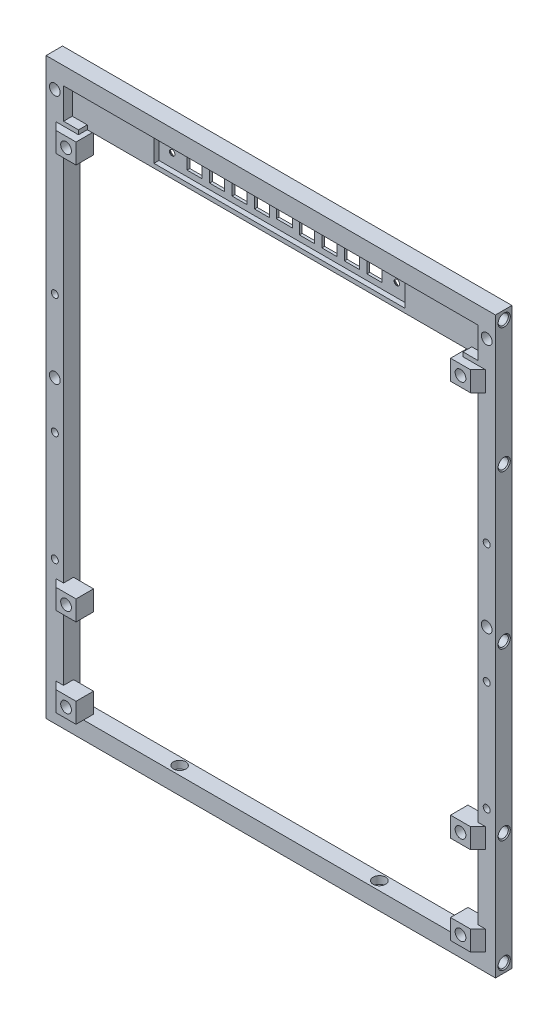
SolidWorks part; units mm, degrees
ref_plane "Front Plane" through (0, 0, 0) normal (0, 0, 1) x (1, 0, 0)
ref_plane "Top Plane" through (0, 0, 0) normal (0, 1, 0) x (1, 0, 0)
ref_plane "Right Plane" through (0, 0, 0) normal (1, 0, 0) x (0, 0, -1)
sketch "Sketch1" plane through (0, 0, 0) normal (0, 0, 1) x (1, 0, 0)
  line L1 (-90, -115) -> (90, -115)
  line L2 (-90, -115) -> (-90, 115)
  line L3 (-90, 115) -> (90, 115)
  line L4 (90, -115) -> (90, 115)
  line L5 (-90, -115) -> (90, 115) construction
  line L6 (-90, 115) -> (90, -115) construction
  line L7 (-83, -108) -> (83, -108)
  line L8 (-83, -108) -> (-83, 108)
  line L9 (-83, 108) -> (83, 108)
  line L10 (83, -108) -> (83, 108)
  line L11 (-83, -108) -> (83, 108) construction
  line L12 (-83, 108) -> (83, -108) construction
  point P0 (0, 0)
  point P6 (0, 0)
  dimension "D1" = 180
  dimension "D2" = 230
  dimension "D3" = 7
  dimension "D4" = 7
extrude "Boss-Extrude1" add sketch "Sketch1" along normal blind 7
sketch "Sketch2" plane through (-90, 0, 0) normal (-1, 0, 0) x (0, 0, 1)
  line L0 (3.5, 111.5) -> (3.5, -111.5) construction
  line L1 (7, 115) -> (0, 115) construction
  circle A0 centre (3.5, -111.5) radius 2.05
  circle A2 centre (3.5, 111.5) radius 2.05
  circle A3 centre (3.5, 61.5) radius 2.05
  circle A4 centre (3.5, -66.5) radius 2.05
  point P2 (3.5, 0)
  point P7 (3.5, 115)
  dimension "D2" = 4.1
  dimension "D3" = 50
  dimension "D4" = 45
  dimension "D1" = 3.5
extrude "Cut-Extrude1" cut sketch "Sketch2" against normal blind 6
mirror "Mirror1" about plane through (0, 0, 0) normal (1, 0, 0) of "Cut-Extrude1"
sketch "Sketch3" plane through (0, -108, 0) normal (0, 1, 0) x (1, 0, 0)
  line L0 (0, 0) -> (0, -7) construction
  line L1 (-83, 0) -> (83, 0) construction
  line L2 (-83, -7) -> (83, -7) construction
  line L3 (40, -3.5) -> (-40, -3.5) construction
  circle A0 centre (40, -3.5) radius 1.35
  circle A1 centre (-40, -3.5) radius 1.35
  point P9 (0, -3.5)
  dimension "D1" = 2.7
  dimension "D2" = 80
extrude "Cut-Extrude2" cut sketch "Sketch3" against normal through all
sketch "Sketch4" plane through (0, -108, 0) normal (0, 1, 0) x (1, 0, 0)
  circle A0 centre (40, -3.5) radius 2.5
  circle A1 centre (-40, -3.5) radius 2.5
  dimension "D1" = 5
extrude "Cut-Extrude3" cut sketch "Sketch4" against normal blind 3
sketch "Sketch5" plane through (0, 0, 0) normal (0, 0, -1) x (-1, 0, 0)
  line L0 (-86.5, -115) -> (-86.5, 115) construction
  line L1 (90, -115) -> (-90, -115) construction
  line L2 (-90, 115) -> (90, 115) construction
  line L3 (-83, 0) -> (-90, 0) construction
  line L4 (-83, -108) -> (-83, 108) construction
  line L5 (-90, -115) -> (-90, 115) construction
  line L6 (0, 115) -> (0, -115) construction
  line L7 (83, -108) -> (-83, -108) construction
  circle A0 centre (-86.5, 34) radius 1.4
  circle A1 centre (86.5, 34) radius 1.4
  circle A2 centre (-86.5, -58) radius 1.4
  circle A3 centre (86.5, -58) radius 1.4
  point P12 (-86.5, 0)
  point P13 (-86.5, 0)
  dimension "D1" = 2.8
  dimension "D2" = 34
  dimension "D3" = 50
extrude "Cut-Extrude4" cut sketch "Sketch5" against normal through all
sketch "Sketch6" plane through (0, 0, 0) normal (0, 0, -1) x (-1, 0, 0)
  circle A0 centre (-86.5, 34) radius 2.5
  circle A1 centre (86.5, 34) radius 2.5
  circle A2 centre (-86.5, -58) radius 2.5
  circle A3 centre (86.5, -58) radius 2.5
  dimension "D1" = 5
extrude "Cut-Extrude5" cut sketch "Sketch6" against normal blind 3
sketch "Sketch7" plane through (0, 0, 0) normal (0, 0, -1) x (-1, 0, 0)
  line L0 (-83, 108) -> (-90, 108) construction
  line L1 (-90, -115) -> (-90, 115) construction
  line L2 (-86.5, 105) -> (-86.5, 5) construction
  line L3 (-90, 115) -> (90, 115) construction
  circle A0 centre (-86.5, 105) radius 2.15
  circle A1 centre (-86.5, 5) radius 2.15
  point P8 (-86.5, 108)
  dimension "D1" = 4.3
  dimension "D2" = 10
  dimension "D3" = 100
extrude "Cut-Extrude6" cut sketch "Sketch7" against normal through all
mirror "Mirror2" about plane through (0, 0, 0) normal (1, 0, 0) of "Cut-Extrude6"
sketch "Sketch8" plane through (0, 0, 3) normal (0, 0, -1) x (-1, 0, 0)
  line L2 (-87.9, 31.9288) -> (-87.9, 36.0712)
  line L4 (-85.1, 31.9288) -> (-85.1, 36.0712)
  line L5 (-87.9, 31.9288) -> (-85.1, 36.0712) construction
  line L6 (-87.9, 36.0712) -> (-85.1, 31.9288) construction
  line L8 (-87.9, -60.0712) -> (-87.9, -55.9288)
  line L10 (-85.1, -60.0712) -> (-85.1, -55.9288)
  line L11 (-87.9, -60.0712) -> (-85.1, -55.9288) construction
  line L12 (-87.9, -55.9288) -> (-85.1, -60.0712) construction
  circle A0 centre (-86.5, 34) radius 2.5 construction
  circle A1 centre (-86.5, -58) radius 2.5 construction
  circle A2 centre (-86.5, -58) radius 2.5 construction
  arc A3 (-85.1, 36.0712) -> (-87.9, 36.0712) centre (-86.5, 34) ccw
  arc A4 (-85.1, -55.9288) -> (-87.9, -55.9288) centre (-86.5, -58) ccw
  circle A5 centre (-86.5, 34) radius 1.4 construction
  circle A6 centre (-86.5, -58) radius 1.4 construction
  arc A7 (-87.9, -60.0712) -> (-85.1, -60.0712) centre (-86.5, -58) ccw
  arc A8 (-87.9, 31.9288) -> (-85.1, 31.9288) centre (-86.5, 34) ccw
  point P0 (-86.5, 34)
  point P8 (-86.5, -58)
extrude "Cut-Extrude7" cut sketch "Sketch8" against normal blind 0.2
sketch "Sketch9" plane through (0, 0, 3.2) normal (0, 0, -1) x (-1, 0, 0)
  line L0 (-85.1, 34) -> (-85.1, 36.0712) construction
  line L1 (-87.9, 32.6) -> (-85.1, 32.6)
  line L2 (-87.9, 32.6) -> (-87.9, 35.4)
  line L3 (-87.9, 35.4) -> (-85.1, 35.4)
  line L4 (-85.1, 32.6) -> (-85.1, 35.4)
  line L5 (-87.9, 32.6) -> (-85.1, 35.4) construction
  line L6 (-87.9, 35.4) -> (-85.1, 32.6) construction
  line L7 (-85.1, -60.0712) -> (-85.1, -55.9288) construction
  line L8 (-87.9, -59.4) -> (-85.1, -59.4)
  line L9 (-87.9, -59.4) -> (-87.9, -56.6)
  line L10 (-87.9, -56.6) -> (-85.1, -56.6)
  line L11 (-85.1, -59.4) -> (-85.1, -56.6)
  line L12 (-87.9, -59.4) -> (-85.1, -56.6) construction
  line L13 (-87.9, -56.6) -> (-85.1, -59.4) construction
  arc A0 (-85.1, 34) -> (-87.9, 34) centre (-86.5, 34) ccw construction
  point P0 (-86.5, 34)
  point P8 (-86.5, -58)
extrude "Cut-Extrude8" cut sketch "Sketch9" against normal blind 0.2
mirror "Mirror3" about plane through (0, 0, 0) normal (1, 0, 0) of "Cut-Extrude8", "Cut-Extrude7"
sketch "Sketch10" plane through (0, 0, 7) normal (0, 0, 1) x (1, 0, 0)
  line L0 (83, -108) -> (83, 108) construction
  line L1 (83, -108) -> (77, -108)
  line L2 (83, -108) -> (83, -102)
  line L3 (83, -102) -> (77, -102)
  line L4 (77, -108) -> (77, -102)
  line L5 (83, -78.5) -> (77, -78.5)
  line L6 (83, -78.5) -> (83, -72.5)
  line L7 (83, -72.5) -> (77, -72.5)
  line L8 (77, -78.5) -> (77, -72.5)
  line L9 (-83, -108) -> (83, -108) construction
  dimension "D1" = 6
  dimension "D2" = 35.5
extrude "Boss-Extrude2" add sketch "Sketch10" against normal offset from surface (5.5 mm away) 1.5 up to face at (-84.35, 5, 0)
sketch "Sketch11" plane through (0, 0, 1.5) normal (0, 0, -1) x (-1, 0, 0)
  line L0 (-83, -78.5) -> (-77, -72.5) construction
  line L2 (-83, -108) -> (-77, -102) construction
  circle A0 centre (-80, -75.5) radius 1.65
  circle A1 centre (-80, -105) radius 1.65
  dimension "D1" = 3.3
extrude "Cut-Extrude9" cut sketch "Sketch11" against normal through all
mirror "Mirror4" about plane through (0, 0, 0) normal (1, 0, 0) of "Cut-Extrude9", "Boss-Extrude2"
sketch "Sketch12" plane through (0, 0, 0) normal (0, 0, -1) x (-1, 0, 0)
  line L0 (83, 108) -> (83, -108) construction
  line L1 (-83, 108) -> (83, 108)
  line L2 (-83, 108) -> (-83, 94)
  line L3 (-83, 94) -> (83, 94)
  line L4 (83, 108) -> (83, 94)
  dimension "D1" = 14
extrude "Boss-Extrude3" add sketch "Sketch12" against normal blind 1.5
sketch "Sketch13" plane through (0, 0, 1.5) normal (0, 0, 1) x (1, 0, 0)
  line L0 (-83, 108) -> (83, 94) construction
  line L2 (-50.3, 95.7) -> (50.3, 95.7)
  line L3 (-50.3, 95.7) -> (-50.3, 106.3)
  line L4 (-50.3, 106.3) -> (50.3, 106.3)
  line L5 (50.3, 95.7) -> (50.3, 106.3)
  line L6 (-50.3, 95.7) -> (50.3, 106.3) construction
  line L7 (-50.3, 106.3) -> (50.3, 95.7) construction
  line L8 (-83, 94) -> (83, 94)
  line L9 (-83, 94) -> (-83, 108)
  line L10 (-83, 108) -> (83, 108)
  line L11 (83, 94) -> (83, 108)
  line L12 (-83, 94) -> (83, 108) construction
  line L13 (-83, 108) -> (83, 94) construction
  point P4 (0, 101)
  point P9 (0, 101)
  dimension "D1" = 100.6
  dimension "D2" = 10.6
extrude "Boss-Extrude4" add sketch "Sketch13" along normal blind 2
sketch "Sketch14" plane through (0, 0, 1.5) normal (0, 0, 1) x (1, 0, 0)
  line L0 (0, 106.3) -> (0, 95.7) construction
  line L1 (50.3, 106.3) -> (-50.3, 106.3) construction
  line L2 (-50.3, 95.7) -> (50.3, 95.7) construction
  line L3 (-50.3, 101) -> (50.3, 101) construction
  line L4 (50.3, 95.7) -> (50.3, 106.3) construction
  line L5 (-33, 104) -> (-39, 104)
  line L6 (-3.25, 99) -> (3.25, 99)
  line L7 (-3.25, 99) -> (-3.25, 103)
  line L8 (-3.25, 103) -> (3.25, 103)
  line L9 (3.25, 99) -> (3.25, 103)
  line L10 (-3.25, 99) -> (3.25, 103) construction
  line L11 (-3.25, 103) -> (3.25, 99) construction
  line L12 (6, 98) -> (12, 98)
  line L13 (6, 98) -> (6, 104)
  line L14 (6, 104) -> (12, 104)
  line L15 (12, 98) -> (12, 104)
  line L16 (6, 98) -> (12, 104) construction
  line L17 (6, 104) -> (12, 98) construction
  line L18 (15, 98) -> (21, 98)
  line L19 (15, 98) -> (15, 104)
  line L20 (15, 104) -> (21, 104)
  line L21 (21, 98) -> (21, 104)
  line L22 (15, 98) -> (21, 104) construction
  line L23 (15, 104) -> (21, 98) construction
  line L24 (24, 98) -> (30, 98)
  line L25 (24, 98) -> (24, 104)
  line L26 (24, 104) -> (30, 104)
  line L27 (30, 98) -> (30, 104)
  line L28 (24, 98) -> (30, 104) construction
  line L29 (24, 104) -> (30, 98) construction
  line L30 (33, 98) -> (39, 98)
  line L31 (33, 98) -> (33, 104)
  line L32 (33, 104) -> (39, 104)
  line L33 (39, 98) -> (39, 104)
  line L34 (33, 98) -> (39, 104) construction
  line L35 (33, 104) -> (39, 98) construction
  line L36 (-39, 98) -> (-39, 104)
  line L37 (-33, 98) -> (-39, 98)
  line L38 (-33, 98) -> (-33, 104)
  line L39 (-24, 104) -> (-30, 104)
  line L40 (-30, 98) -> (-30, 104)
  line L41 (-24, 98) -> (-30, 98)
  line L42 (-24, 98) -> (-24, 104)
  line L43 (-15, 104) -> (-21, 104)
  line L44 (-21, 98) -> (-21, 104)
  line L45 (-15, 98) -> (-21, 98)
  line L46 (-15, 98) -> (-15, 104)
  line L47 (-6, 104) -> (-12, 104)
  line L48 (-12, 98) -> (-12, 104)
  line L49 (-6, 98) -> (-12, 98)
  line L50 (-6, 98) -> (-6, 104)
  circle A0 centre (-45, 101) radius 1.3 construction
  circle A1 centre (45, 101) radius 1.3 construction
  point P6 (0, 101)
  point P11 (0, 101)
  point P16 (9, 101)
  point P21 (18, 101)
  point P26 (27, 101)
  point P31 (36, 101)
  dimension "D10" = 2.6
  dimension "D9" = 45
  dimension "D1" = 6.5
  dimension "D2" = 4
  dimension "D3" = 6
  dimension "D4" = 9
  dimension "D5" = 9
  dimension "D6" = 9
  dimension "D7" = 9
  dimension "D8" = 45
extrude "Cut-Extrude10" cut sketch "Sketch14" against normal through all
sketch "Sketch15" plane through (0, 0, 1.5) normal (0, 0, 1) x (1, 0, 0)
  circle A0 centre (-45, 101) radius 1
  circle A1 centre (45, 101) radius 1
  dimension "D1" = 2
extrude "Boss-Extrude5" add sketch "Sketch15" along normal up to surface (2 mm away) up to face at (0, 101, 3.5)
chamfer "Chamfer1" distance 0.4 angle 45 3 edges at (-83, -7, 0) (83, -7, 0) (0, -108, 0) tangent propagation no
chamfer "Chamfer2" distance 0.4 angle 45 4 edges at (0, 115, 0) (-90, 0, 0) (0, -115, 0) (90, 0, 0)
chamfer "Chamfer3" distance 0.4 angle 45 36 edges at (-36, 98, 0) (-39, 101, 0) (-36, 104, 0) (-33, 101, 0) (-27, 98, 0) (-30, 101, 0) (-27, 104, 0) (-24, 101, 0) (-18, 98, 0) (-21, 101, 0) (-18, 104, 0) (-15, 101, 0) (-9, 98, 0) (-12, 101, 0) (-9, 104, 0) (-6, 101, 0) (0, 99, 0) (-3.25, 101, 0) (0, 103, 0) (3.25, 101, 0) (9, 98, 0) (6, 101, 0) (9, 104, 0) (12, 101, 0) (18, 98, 0) (15, 101, 0) (18, 104, 0) (21, 101, 0) (36, 98, 0) (33, 101, 0) (36, 104, 0) (39, 101, 0) (27, 98, 0) (24, 101, 0) (27, 104, 0) (30, 101, 0)
sketch "Sketch16" plane through (0, 0, 7) normal (0, 0, 1) x (1, 0, 0)
  line L0 (-77, 94) -> (-77, 95.7)
  line L1 (-83, -72.5) -> (-77, -72.5)
  line L2 (-83, -72.5) -> (-83, -66.5)
  line L3 (-83, -66.5) -> (-77, -66.5)
  line L4 (-77, -72.5) -> (-77, -66.5)
  line L5 (83, -72.5) -> (77, -72.5)
  line L6 (83, -72.5) -> (83, -66.5)
  line L7 (83, -66.5) -> (77, -66.5)
  line L8 (77, -72.5) -> (77, -66.5)
  line L9 (83, 94) -> (77, 94) construction
  line L10 (83, 94) -> (83, 88)
  line L11 (83, 88) -> (77, 88)
  line L12 (77, 94) -> (77, 88)
  line L13 (-83, 94) -> (-77, 94) construction
  line L14 (-83, 94) -> (-83, 88)
  line L15 (-83, 88) -> (-77, 88)
  line L16 (-77, 94) -> (-77, 88)
  line L17 (-50.3, 95.7) -> (50.3, 95.7) construction
  line L18 (-77, 95.7) -> (-83, 95.7)
  line L19 (-83, 108) -> (-83, 94) construction
  line L20 (-83, 95.7) -> (-83, 94)
  line L21 (77, 94) -> (77, 95.7)
  line L22 (77, 95.7) -> (83, 95.7)
  line L23 (83, 94) -> (83, 108) construction
  line L24 (83, 95.7) -> (83, 94)
  dimension "D1" = 6
extrude "Boss-Extrude7" add sketch "Sketch16" against normal offset from surface (5.5 mm away) 1.5 up to face at (-36, 101, 0)
sketch "Sketch17" plane through (0, 0, 1.5) normal (0, 0, -1) x (-1, 0, 0)
  line L0 (-77, 88) -> (77, -66.5) construction
  line L1 (-77, -66.5) -> (-77, -78.5) construction
  line L2 (-80, -69.5) -> (80, -69.5) construction
  line L3 (-80, -69.5) -> (-80, 91) construction
  line L4 (-80, 91) -> (80, 91) construction
  line L5 (80, -69.5) -> (80, 91) construction
  line L6 (-80, -69.5) -> (80, 91) construction
  line L7 (-80, 91) -> (80, -69.5) construction
  line L8 (77, -66.5) -> (83, -66.5) construction
  circle A0 centre (-80, -69.5) radius 1.65
  circle A1 centre (80, -69.5) radius 1.65
  circle A2 centre (80, 91) radius 1.65
  circle A3 centre (-80, 91) radius 1.65
  point P4 (0, 10.75)
  dimension "D3" = 3.3
  dimension "D1" = 3
  dimension "D2" = 3
extrude "Cut-Extrude11" cut sketch "Sketch17" against normal through all
sketch "Sketch18" plane through (0, 0, 1.5) normal (0, 0, 1) x (1, 0, 0)
  circle A0 centre (-45, 101) radius 1.1
  circle A1 centre (45, 101) radius 1.1
  dimension "D1" = 2.2
extrude "Cut-Extrude12" cut sketch "Sketch18" against normal through all both and the other way through all
chamfer "Chamfer4" distance 1.3 angle 45 2 edges at (-43.9, 101, 0) (46.1, 101, 0)
sketch "Sketch19" plane through (0, 0, 1.5) normal (0, 0, -1) x (-1, 0, 0)
  line L1 (-83, -108) -> (83, -108)
  line L2 (-83, -108) -> (-83, 94)
  line L3 (-83, 94) -> (83, 94)
  line L4 (83, -108) -> (83, 94)
extrude "Cut-Extrude13" cut sketch "Sketch19" against normal through all
ref_plane "Plane1" through (0, 0, 3) normal (0, 0, 1) x (1, 0, 0)
sketch "Sketch20" plane through (0, 0, 3) normal (0, 0, 1) x (1, 0, 0)
  line L0 (83, 94) -> (83, -108) construction
  line L1 (83, -108) -> (75, -108)
  line L2 (83, -108) -> (83, -100)
  line L3 (83, -100) -> (75, -100)
  line L4 (75, -108) -> (75, -100)
  line L5 (83, 94) -> (75, 94)
  line L6 (83, 94) -> (83, 86)
  line L7 (83, 86) -> (75, 86)
  line L8 (75, 94) -> (75, 86)
  line L9 (83, -64.5) -> (75, -64.5)
  line L10 (83, -64.5) -> (83, -72.5)
  line L11 (83, -72.5) -> (75, -72.5)
  line L12 (75, -64.5) -> (75, -72.5)
  dimension "D1" = 8
  dimension "D2" = 27.5
extrude "Boss-Extrude8" add sketch "Sketch20" along normal blind 7
sketch "Sketch21" plane through (0, 0, 3) normal (0, 0, -1) x (-1, 0, 0)
  line L0 (-75, 94) -> (-83, 86) construction
  line L1 (-83, -100) -> (-75, -108) construction
  line L2 (-83, -64.5) -> (-75, -72.5) construction
  circle A0 centre (-79, 90) radius 2.15
  circle A1 centre (-79, -104) radius 2.15
  circle A2 centre (-79, -68.5) radius 2.15
  dimension "D1" = 4.3
extrude "Cut-Extrude14" cut sketch "Sketch21" against normal through all
mirror "Mirror5" about plane through (0, 0, 0) normal (1, 0, 0) of "Cut-Extrude14", "Boss-Extrude8"
chamfer "Chamfer5" distance 3 angle 45 6 edges at (-83, -104, 7) (83, -104, 7) (83, 90, 7) (-83, 90, 7) (-83, -68.5, 7) (83, -68.5, 7)
sketch "Sketch23" plane through (0, 0, 0) normal (0, 0, -1) x (-1, 0, 0)
  line L0 (-83.4, 94) -> (83.4, 94) construction
  line L1 (-15, 94) -> (15, 94)
  line L2 (-15, 94) -> (-15, 69)
  line L3 (-15, 69) -> (15, 69)
  line L4 (15, 94) -> (15, 69)
  point P6 (0, 69)
  dimension "D1" = 25
  dimension "D2" = 30
extrude "Boss-Extrude10" add sketch "Sketch23" against normal up to surface (3.5 mm away) up to face at (0, 97.48, 3.5)
sketch "Sketch24" plane through (0, 0, 3.5) normal (0, 0, 1) x (1, 0, 0)
  line L0 (15, 69) -> (-15, 69) construction
  line L1 (-12.7, 69) -> (12.7, 69)
  line L2 (-12.7, 69) -> (-12.7, 94)
  line L3 (-12.7, 94) -> (12.7, 94)
  line L4 (12.7, 69) -> (12.7, 94)
  line L5 (-75, 94) -> (-15, 94) construction
  point P6 (0, 69)
  dimension "D1" = 25.4
extrude "Cut-Extrude15" cut sketch "Sketch24" against normal offset from surface (2.5 mm away) 1 up to face at (-47.4, 101, 0)
sketch "Sketch26" plane through (0, 0, 1) normal (0, 0, 1) x (1, 0, 0)
  line L0 (12.7, 94) -> (-12.7, 94) construction
  line L1 (-12.5, 93.4) -> (12.5, 93.4) construction
  line L2 (-12.5, 93.4) -> (-12.5, 69.538) construction
  line L3 (-12.5, 69.538) -> (12.5, 69.538) construction
  line L4 (12.5, 93.4) -> (12.5, 69.538) construction
  line L5 (0, 93.4) -> (0, 69.538) construction
  line L6 (-10.5, 91.4) -> (10.5, 91.4) construction
  line L7 (-10.5, 91.4) -> (-10.5, 78.9) construction
  line L8 (-10.5, 78.9) -> (10.5, 78.9) construction
  line L9 (10.5, 91.4) -> (10.5, 78.9) construction
  line L10 (12.7, 94) -> (-12.7, 94) construction
  line L11 (-5.4, 73.6) -> (5.4, 73.6) construction
  line L12 (-5.4, 73.6) -> (-5.4, 84.4) construction
  line L13 (-5.4, 84.4) -> (5.4, 84.4) construction
  line L14 (5.4, 73.6) -> (5.4, 84.4) construction
  line L15 (-5.4, 73.6) -> (5.4, 84.4) construction
  line L16 (-5.4, 84.4) -> (5.4, 73.6) construction
  circle A0 centre (-10.5, 91.4) radius 1.1 construction
  circle A1 centre (10.5, 91.4) radius 1.1 construction
  circle A2 centre (10.5, 78.9) radius 1.1 construction
  circle A3 centre (-10.5, 78.9) radius 1.1 construction
  point P4 (0, 93.4)
  point P7 (0, 94)
  point P12 (0, 91.4)
  point P19 (0, 79)
  dimension "D3" = 2.2
  dimension "D1" = 25
  dimension "D2" = 23.862
  dimension "D4" = 2
  dimension "D5" = 14.5
  dimension "D6" = 10.8
  dimension "D7" = 10.8
  dimension "D8" = 14.4
  dimension "D9" = 0.6
  dimension "D10" = 2
sketch "Sketch27" plane through (0, 0, 1) normal (0, 0, 1) x (1, 0, 0)
  line L0 (-12.7, 94) -> (-12.7, 69) construction
  line L1 (-12.7, 94) -> (-8.5, 94)
  line L2 (-12.7, 94) -> (-12.7, 89.4)
  line L3 (-12.7, 89.4) -> (-8.5, 89.4)
  line L4 (-8.5, 94) -> (-8.5, 89.4)
  line L5 (-12.7, 76.9) -> (-8.5, 76.9)
  line L6 (-12.7, 76.9) -> (-12.7, 80.9)
  line L7 (-12.7, 80.9) -> (-8.5, 80.9)
  line L8 (-8.5, 76.9) -> (-8.5, 80.9)
  line L9 (0, 94) -> (0, 69) construction
  line L10 (12.7, 94) -> (-12.7, 94) construction
  line L11 (-12.7, 69) -> (12.7, 69) construction
  line L12 (8.5, 76.9) -> (8.5, 80.9)
  line L13 (12.7, 80.9) -> (8.5, 80.9)
  line L14 (12.7, 76.9) -> (12.7, 80.9)
  line L15 (12.7, 76.9) -> (8.5, 76.9)
  line L16 (8.5, 94) -> (8.5, 89.4)
  line L17 (12.7, 89.4) -> (8.5, 89.4)
  line L18 (12.7, 94) -> (12.7, 89.4)
  line L19 (12.7, 94) -> (8.5, 94)
  dimension "D1" = 2
  dimension "D2" = 2
  dimension "D3" = 2
  dimension "D4" = 2
  dimension "D5" = 2
extrude "Boss-Extrude11" add sketch "Sketch27" along normal blind 3
sketch "Sketch28" plane through (0, 0, 1) normal (0, 0, 1) x (1, 0, 0)
  line L0 (-5.4, 84.4) -> (5.4, 84.4) construction
  line L1 (-6, 73) -> (6, 73)
  line L2 (-6, 73) -> (-6, 85)
  line L3 (-6, 85) -> (6, 85)
  line L4 (6, 73) -> (6, 85)
  line L5 (-6, 73) -> (6, 85) construction
  line L6 (-6, 85) -> (6, 73) construction
  line L7 (5.4, 73.6) -> (5.4, 84.4) construction
  point P0 (0, 79)
  dimension "D1" = 0.6
  dimension "D2" = 0.6
extrude "Cut-Extrude16" cut sketch "Sketch28" against normal through all
sketch "Sketch29" plane through (0, 0, 4) normal (0, 0, 1) x (1, 0, 0)
  circle A0 centre (-10.5, 78.9) radius 1.1
  circle A1 centre (-10.5, 91.4) radius 1.1
  circle A2 centre (10.5, 91.4) radius 1.1
  circle A3 centre (10.5, 78.9) radius 1.1
  dimension "D1" = 2.2
extrude "Cut-Extrude17" cut sketch "Sketch29" against normal through all
chamfer "Chamfer6" distance 1.3 angle 45 4 edges at (11.6, 78.9, 0) (-9.4, 78.9, 0) (-9.4, 91.4, 0) (11.6, 91.4, 0)
chamfer "Chamfer7" distance 0.4 angle 45 4 edges at (0, 73, 0) (-6, 79, 0) (0, 85, 0) (6, 79, 0)
chamfer "Chamfer8" distance 0.4 angle 45 2 edges at (-49.2, 94, 0) (49.2, 94, 0)
sketch "Sketch30" plane through (0, 0, 3.5) normal (0, 0, 1) x (1, 0, 0)
  line L0 (-12.7, 69) -> (-12.7, 94)
  line L1 (-12.7, 94) -> (12.7, 94)
  line L2 (12.7, 94) -> (12.7, 69)
  line L3 (12.7, 69) -> (15, 69)
  line L4 (15, 69) -> (15, 95.7)
  line L5 (-50.3, 95.7) -> (50.3, 95.7) construction
  line L6 (15, 95.7) -> (-15, 95.7)
  line L7 (-15, 95.7) -> (-15, 69)
  line L8 (-12.7, 69) -> (-15, 69)
extrude "Boss-Extrude12" add sketch "Sketch30" along normal blind 3
chamfer "Chamfer9" distance 0.4 angle 45 18 edges at (-76.85, -104, 3) (-84.35, 5, 0) (-76.85, -68.5, 3) (-76.85, 90, 3) (-84.35, 105, 0) (76.85, -104, 3) (76.85, -68.5, 3) (76.85, 90, 3) (84.35, 5, 0) (84.35, 105, 0) (90, 111.5, 5.55) (90, 61.5, 5.55) (90, -66.5, 5.55) (90, -111.5, 5.55) (-90, -111.5, 5.55) (-90, -66.5, 5.55) (-90, 61.5, 5.55) (-90, 111.5, 5.55)
sketch "Sketch31" plane through (0, 0, 0) normal (0, 0, -1) x (-1, 0, 0)
  line L1 (-15, 69) -> (15, 69)
  line L2 (-15, 69) -> (-15, 94)
  line L3 (-15, 94) -> (15, 94)
  line L4 (15, 69) -> (15, 94)
extrude "Cut-Extrude18" cut sketch "Sketch31" against normal through all
sketch "Sketch32" plane through (-15, 0, 0) normal (-1, 0, 0) x (0, 0, 1)
  line L4 (3.5, 94) -> (6.5, 94)
  line L5 (6.5, 94) -> (6.5, 95.7)
  line L6 (6.5, 95.7) -> (3.5, 95.7)
  line L7 (3.5, 95.7) -> (3.5, 94)
  line L8 (3.5, 94) -> (6.5, 94)
  line L9 (6.5, 94) -> (6.5, 95.7)
  line L10 (6.5, 95.7) -> (3.5, 95.7)
  line L11 (3.5, 95.7) -> (3.5, 94)
  dimension "D1" = 0
extrude "Cut-Extrude19" cut sketch "Sketch32" against normal up to surface (30 mm away) up to face at (15, 94.85, 5)
chamfer "Chamfer10" distance 0.4 angle 45 1 edges at (0, 94, 0)
sketch "Sketch33" plane through (0, 0, 0) normal (0, 0, -1) x (-1, 0, 0)
  line L0 (90, -115) -> (-90, -115) construction
  circle A0 centre (-86.5, -14) radius 1.4
  arc A1 (-87.9, 34) -> (-86.5, 32.6) centre (-86.5, 34) ccw construction
  point P3 (-86.5, 34)
  dimension "D1" = 101
extrude "Cut-Extrude20" cut sketch "Sketch33" against normal through all
mirror "Mirror6" about plane through (0, 0, 0) normal (1, 0, 0) of "Cut-Extrude20"
sketch "Sketch34" plane through (0, 0, 0) normal (0, 0, -1) x (-1, 0, 0)
  circle A0 centre (-86.5, -14) radius 2.5
  circle A1 centre (-86.5, -58) radius 2.5 construction
extrude "Cut-Extrude21" cut sketch "Sketch34" against normal up to surface (3 mm away) up to face at (84.55, -58, 3)
sketch "Sketch35" plane through (0, 0, 3) normal (0, 0, -1) x (-1, 0, 0)
  line L2 (-87.9, -16.0712) -> (-87.9, -11.9288)
  line L4 (-85.1, -16.0712) -> (-85.1, -11.9288)
  line L5 (-87.9, -16.0712) -> (-85.1, -11.9288) construction
  line L6 (-87.9, -11.9288) -> (-85.1, -16.0712) construction
  circle A0 centre (-86.5, -14) radius 2.5 construction
  circle A1 centre (-86.5, -14) radius 1.4 construction
  circle A2 centre (-86.5, -14) radius 2.5 construction
  arc A3 (-85.1, -11.9288) -> (-87.9, -11.9288) centre (-86.5, -14) ccw
  arc A4 (-87.9, -16.0712) -> (-85.1, -16.0712) centre (-86.5, -14) ccw
  point P0 (-86.5, -14)
extrude "Cut-Extrude22" cut sketch "Sketch35" against normal blind 0.2
sketch "Sketch36" plane through (0, 0, 3.2) normal (0, 0, -1) x (-1, 0, 0)
  line L0 (-85.1, -16.0712) -> (-85.1, -11.9288) construction
  line L1 (-87.9, -15.4) -> (-85.1, -15.4)
  line L2 (-87.9, -15.4) -> (-87.9, -12.6)
  line L3 (-87.9, -12.6) -> (-85.1, -12.6)
  line L4 (-85.1, -15.4) -> (-85.1, -12.6)
  line L5 (-87.9, -15.4) -> (-85.1, -12.6) construction
  line L6 (-87.9, -12.6) -> (-85.1, -15.4) construction
  arc A0 (-85.1, -14) -> (-87.9, -14) centre (-86.5, -14) ccw construction
  point P0 (-86.5, -14)
extrude "Cut-Extrude23" cut sketch "Sketch36" against normal blind 0.2
mirror "Mirror7" about plane through (0, 0, 0) normal (1, 0, 0) of "Cut-Extrude23", "Cut-Extrude22", "Cut-Extrude21"
sketch "Sketch37" plane through (-90, 0, 0) normal (-1, 0, 0) x (0, 0, 1)
  circle A0 centre (3.5, 0) radius 2.05
  circle A1 centre (3.5, 61.5) radius 2.05 construction
  point P2 (0, 0)
  point P3 (3.5, 61.5)
  dimension "D1" = 61.5
extrude "Cut-Extrude24" cut sketch "Sketch37" against normal blind 6
chamfer "Chamfer11" distance 0.4 angle 45 1 edges at (-90, 0, 5.55)
mirror "Mirror10" about plane through (0, 0, 0) normal (1, 0, 0) of "Cut-Extrude24"
chamfer "Chamfer12" distance 0.4 angle 45 1 edges at (90, 0, 5.55)
